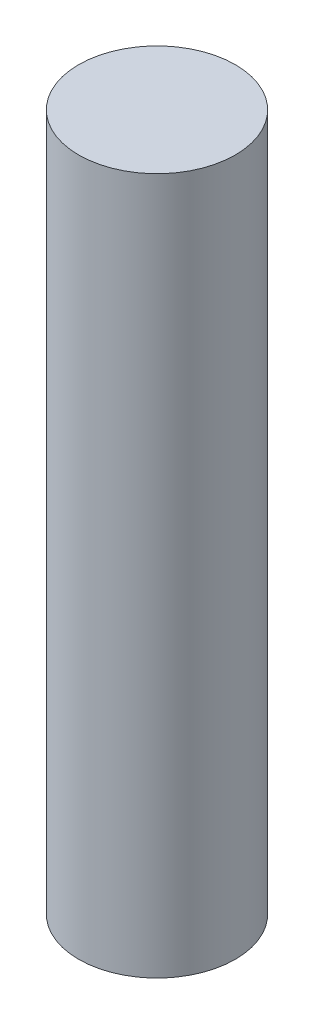
SolidWorks part; units mm, degrees
ref_plane "Front Plane" through (0, 0, 0) normal (0, 0, 1) x (1, 0, 0)
ref_plane "Top Plane" through (0, 0, 0) normal (0, 1, 0) x (1, 0, 0)
ref_plane "Right Plane" through (0, 0, 0) normal (1, 0, 0) x (0, 0, -1)
sketch "Sketch1" plane through (0, 0, 0) normal (0, 1, 0) x (1, 0, 0)
  circle A0 centre (0, 0) radius 12.7
  dimension "D1" = 25.4
extrude "Boss-Extrude1" add sketch "Sketch1" along normal blind 113
equation "\"carbon_fiber_tube_diam\"= 1in, 25.4mm"
equation "\"clip_tube_diam\"= 6mm"
equation "\"middle_tube_len\"= 500mm"
equation "\"horizontal_pipe_spacing\"= 250mm"
equation "\"D1@Sketch1\"=\"carbon_fiber_tube_diam\""
